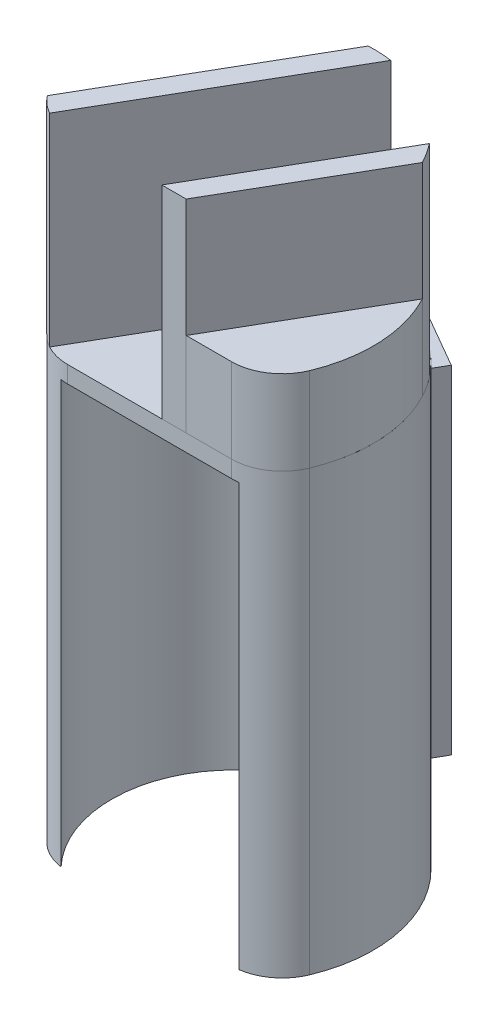
SolidWorks part; units mm, degrees
ref_plane "前视基准面" through (0, 0, 0) normal (0, 0, 1) x (1, 0, 0)
ref_plane "上视基准面" through (0, 0, 0) normal (0, 1, 0) x (1, 0, 0)
ref_plane "右视基准面" through (0, 0, 0) normal (1, 0, 0) x (0, 0, -1)
other "Configuration Table"
sketch "草图1" plane through (0, 0, 0) normal (0, 1, 0) x (1, 0, 0)
  circle A0 centre (0, 0) radius 14.5
  circle A1 centre (0, 0) radius 16.5
  dimension "D1" = 29
  dimension "D2" = 2
extrude "凸台-拉伸1" add sketch "草图1" along normal blind 35
sketch "草图3" plane through (0, 35, 0) normal (0, 1, 0) x (1, 0, 0)
  circle A1 centre (0, 0) radius 16.5
  circle A2 centre (0, 0) radius 16.5
  dimension "D1" = 0
extrude "凸台-拉伸2" add sketch "草图3" along normal blind 2
ref_plane "基准面1" through (0, 0, 10) normal (0, 0, 1) x (1, 0, 0)
sketch "草图4" plane through (0, 0, 10) normal (0, 0, 1) x (1, 0, 0)
  line L1 (-49.9355, 39.7218) -> (28.4145, 39.7218)
  line L2 (-49.9355, 39.7218) -> (-49.9355, -52.0807)
  line L3 (-49.9355, -52.0807) -> (28.4145, -52.0807)
  line L4 (28.4145, 39.7218) -> (28.4145, -52.0807)
extrude "切除-拉伸1" cut sketch "草图4" along normal through all
sketch "草图5" plane through (0, 37, 0) normal (0, 1, 0) x (1, 0, 0)
  circle A0 centre (0, 0) radius 3.75
  dimension "D1" = 7.5
extrude "切除-拉伸2" cut sketch "草图5" against normal up to next
fillet "圆角1" radius 6 2 edges at (-13.1244, 18.5, 10) (13.1244, 18.5, 10)
sketch "草图6" plane through (0, 37, 0) normal (0, 1, 0) x (1, 0, 0)
  line L0 (13.0479, 10.0996) -> (1.4434, -10)
  line L1 (-0.5833, 16.4897) -> (-14.4988, -7.6126)
  line L2 (-24.0688, -10) -> (24.0688, -10) construction
  line L3 (2.2226, 16.3496) -> (-12.5707, -9.2732)
  line L4 (14.5721, 7.7397) -> (4.3301, -10)
  line L5 (-9.7082, -10) -> (9.7082, -10) construction
  line L7 (-9.7082, -10) -> (9.7082, -10)
  line L8 (1.4434, -10) -> (4.3301, -10)
  circle A0 centre (0, 0) radius 6.25 construction
  arc A1 (-15.2558, -6.2857) -> (-9.7082, -10) centre (-9.7082, -4) ccw construction
  arc A2 (15.2558, -6.2857) -> (-15.2558, -6.2857) centre (0, 0) ccw construction
  arc A3 (2.2226, 16.3496) -> (-0.5833, 16.4897) centre (0, 0) ccw
  arc A6 (15.2558, -6.2857) -> (-15.2558, -6.2857) centre (0, 0) ccw
  arc A7 (-15.2558, -6.2857) -> (-9.7082, -10) centre (-9.7082, -4) ccw
  arc A8 (9.7082, -10) -> (15.2558, -6.2857) centre (9.7082, -4) ccw
  arc A9 (14.5721, 7.7397) -> (13.0479, 10.0996) centre (0, 0) ccw
  arc A10 (-14.4988, -7.6126) -> (-12.5707, -9.2732) centre (-9.7082, -4) ccw
  dimension "D1" = 12.5
  dimension "D2" = 60
  dimension "D3" = 2.5
  dimension "D4" = 2.5
  dimension "D5" = 0
extrude "凸台-拉伸3" add sketch "草图6" along normal blind 24 separate body
sketch "草图9" plane through (0, 37, 0) normal (0, 1, 0) x (1, 0, 0)
  line L0 (4.3301, -10) -> (14.5721, 7.7397) construction
  line L1 (-9.7082, -10) -> (9.7082, -10)
  line L2 (4.3301, -10) -> (9.7082, -10)
  line L3 (4.3301, -10) -> (14.5721, 7.7397)
  arc A3 (15.2558, -6.2857) -> (-15.2558, -6.2857) centre (0, 0) ccw
  arc A4 (-15.2558, -6.2857) -> (-9.7082, -10) centre (-9.7082, -4) ccw
  arc A5 (9.7082, -10) -> (15.2558, -6.2857) centre (9.7082, -4) ccw
  arc A6 (15.2558, -6.2857) -> (14.5721, 7.7397) centre (0, 0) ccw
  arc A8 (9.7082, -10) -> (15.2558, -6.2857) centre (9.7082, -4) ccw
  dimension "D1" = 0
extrude "凸台-拉伸7" add sketch "草图9" along normal blind 10 separate body
sketch "草图10" plane through (0, 0, 0) normal (0, -1, 0) x (1, 0, 0)
  arc A4 (-10.5572, 9.9396) -> (10.5572, 9.9396) centre (0, 0) ccw
  arc A6 (-15.2558, 6.2857) -> (15.2558, 6.2857) centre (0, 0) ccw
  arc A10 (-15.2558, 6.2857) -> (15.2558, 6.2857) centre (0, 0) ccw
  arc A13 (-10.5572, 9.9396) -> (10.5572, 9.9396) centre (0, 0) ccw
  arc A16 (-10.5572, 9.9396) -> (-15.2558, 6.2857) centre (-9.7082, 4) ccw
  arc A18 (-10.5572, 9.9396) -> (-15.2558, 6.2857) centre (-9.7082, 4) ccw
  arc A19 (15.2558, 6.2857) -> (10.5572, 9.9396) centre (9.7082, 4) ccw
  arc A20 (15.2558, 6.2857) -> (10.5572, 9.9396) centre (9.7082, 4) ccw
  dimension "D1" = 0
extrude "凸台-拉伸8" add sketch "草图10" along normal blind 15
sketch "草图12" plane through (0, 37, 0) normal (0, 1, 0) x (1, 0, 0)
  line L0 (-11.7068, 12.7233) -> (-15.7072, 5.7943) construction
  line L1 (-0.5833, 16.4897) -> (-14.4988, -7.6126) construction
  line L2 (-14.2894, 8.25) -> (-32.0359, 18.4959) construction
  line L3 (-16.4325, 3.8015) -> (-13.0123, 13.1985)
  line L4 (-13.0123, 13.1985) -> (-10.8657, 12.4172)
  line L5 (-16.4325, 3.8015) -> (-16.0855, 3.6752)
  arc A0 (15.2558, -6.2857) -> (-15.2558, -6.2857) centre (0, 0) ccw construction
  arc A1 (-10.8657, 12.4172) -> (-16.0855, 3.6752) centre (0, 0) ccw
  point P1 (-14.2894, 8.25)
  point P8 (-14.7224, 8.5)
  dimension "D1" = 10
  dimension "D2" = 10
  dimension "D3" = 0.5
extrude "凸台-pos1" add sketch "草图12" against normal blind 40 separate body
sketch "草图13" plane through (0, 37, 0) normal (0, 1, 0) x (1, 0, 0)
  line L0 (3.9199, 16.7894) -> (12.5801, 11.7894) construction
  line L1 (-12.5707, -9.2732) -> (2.2226, 16.3496) construction
  line L2 (4.4199, 17.6554) -> (13.0801, 12.6554)
  line L3 (8.25, 14.2894) -> (4.8925, 8.4741) construction
  line L5 (4.4199, 17.6554) -> (3.532, 16.1175)
  line L6 (13.0801, 12.6554) -> (12.1922, 11.1175)
  arc A0 (15.2558, -6.2857) -> (-15.2558, -6.2857) centre (0, 0) ccw construction
  arc A1 (12.1922, 11.1175) -> (3.532, 16.1175) centre (0, 0) ccw
  point P7 (8.75, 15.1554)
  point P8 (8.25, 14.2894)
  dimension "D1" = 10
  dimension "D2" = 1
extrude "凸台-pos3" add sketch "草图13" against normal blind 40 separate body
sketch "草图14" plane through (0, 37, 0) normal (0, 1, 0) x (1, 0, 0)
  line L0 (-7.1136, 15.176) -> (1.0038, 17.351) construction
  line L1 (13.0801, 12.6554) -> (4.4199, 17.6554) construction
  line L2 (-9.359, 15.6096) -> (0.3003, 18.1978)
  line L3 (-41.0905, 153.3517) -> (-37.2994, 139.2032) construction
  line L4 (-9.359, 15.6096) -> (-8.8993, 13.8943)
  line L5 (0.3003, 18.1978) -> (0.7599, 16.4825)
  arc A0 (15.2558, -6.2857) -> (-15.2558, -6.2857) centre (0, 0) ccw construction
  arc A1 (2.2226, 16.3496) -> (-0.5833, 16.4897) centre (0, 0) ccw construction
  arc A2 (0.7599, 16.4825) -> (-8.8993, 13.8943) centre (0, 0) ccw
  point P9 (-4.2705, 15.9378)
  point P11 (-4.5293, 16.9037)
  dimension "D1" = 135
  dimension "D2" = 10
  dimension "D3" = 1
extrude "凸台-pos2" add sketch "草图14" against normal blind 40 separate body
